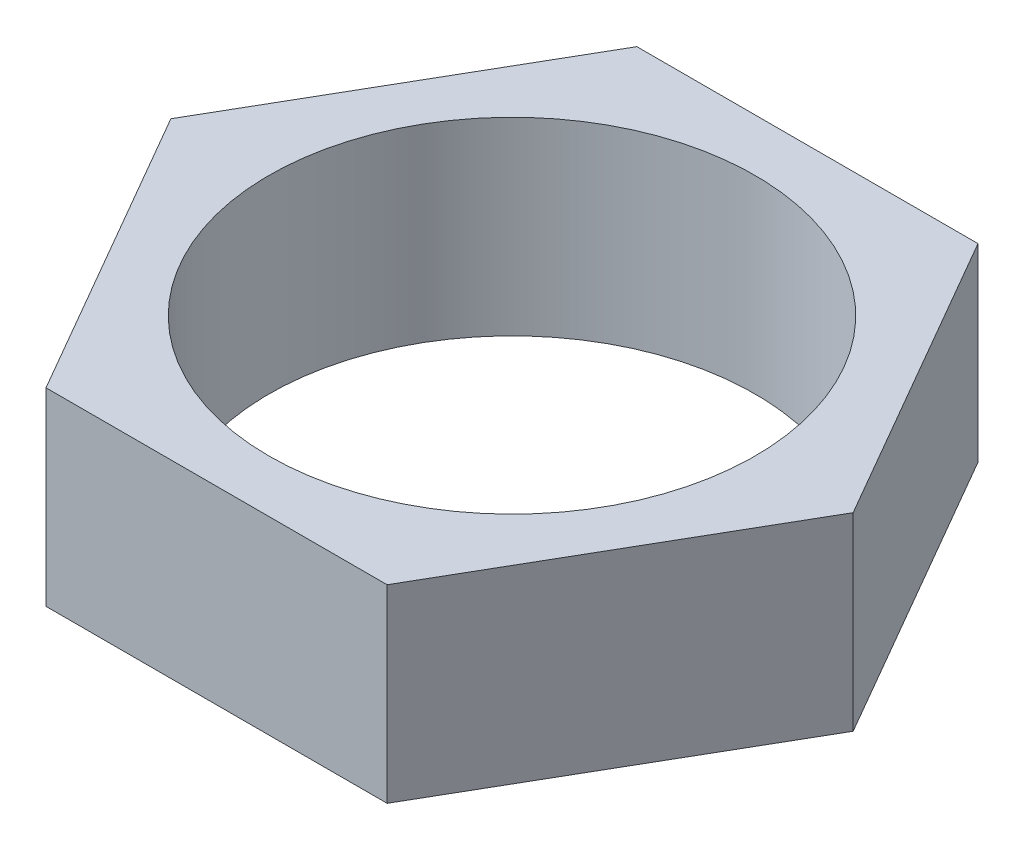
SolidWorks part; units mm, degrees
ref_plane "Front Plane" through (0, 0, 0) normal (0, 0, 1) x (1, 0, 0)
ref_plane "Top Plane" through (0, 0, 0) normal (0, 1, 0) x (1, 0, 0)
ref_plane "Right Plane" through (0, 0, 0) normal (1, 0, 0) x (0, 0, -1)
sketch "Sketch1" plane through (0, 0, 0) normal (0, 1, 0) x (1, 0, 0)
  line L1 (-3.5929, 6.223) -> (-7.1857, 0)
  line L2 (-7.1857, 0) -> (-3.5929, -6.223)
  line L3 (-3.5929, -6.223) -> (3.5929, -6.223)
  line L4 (3.5929, -6.223) -> (7.1857, 0)
  line L5 (7.1857, 0) -> (3.5929, 6.223)
  line L6 (3.5929, 6.223) -> (-3.5929, 6.223)
  circle A0 centre (0, 0) radius 6.223 construction
  circle A1 centre (0, 0) radius 5.12
  dimension "D1" = 12.446
  dimension "D2" = 10.24
extrude "Boss-Extrude1" add sketch "Sketch1" along normal blind 1.9939 and the other way blind 1.9939
sketch "Sketch2" plane through (0, 0, 0) normal (0, 1, 0) x (1, 0, 0)
  circle A0 centre (0, 0) radius 5.12 construction
  circle A1 centre (0, 0) radius 5.12
  circle A2 centre (0, 0) radius 4.9
  dimension "D1" = 9.8
extrude "Boss-Extrude2" [suppressed] add sketch "Sketch2" along normal blind 2.2865 and the other way blind 2.2865
sketch "Sketch3" plane through (0, 0, 0) normal (0, 1, 0) x (1, 0, 0)
  line L0 (-3.5929, 6.223) -> (-7.1857, 0) construction
  line L1 (3.5929, 6.223) -> (-3.5929, 6.223) construction
  line L2 (-4.5412, 4.5804) -> (-3.5929, 6.223)
  line L3 (-3.5929, 6.223) -> (-1.6961, 6.223)
  arc A0 (-4.5412, 4.5804) -> (-1.6961, 6.223) centre (0, 0) cw
  dimension "D1" = 6.45
extrude "Boss-Extrude3" [suppressed] add sketch "Sketch3" along normal blind 6.2865 and the other way blind 6.2865
